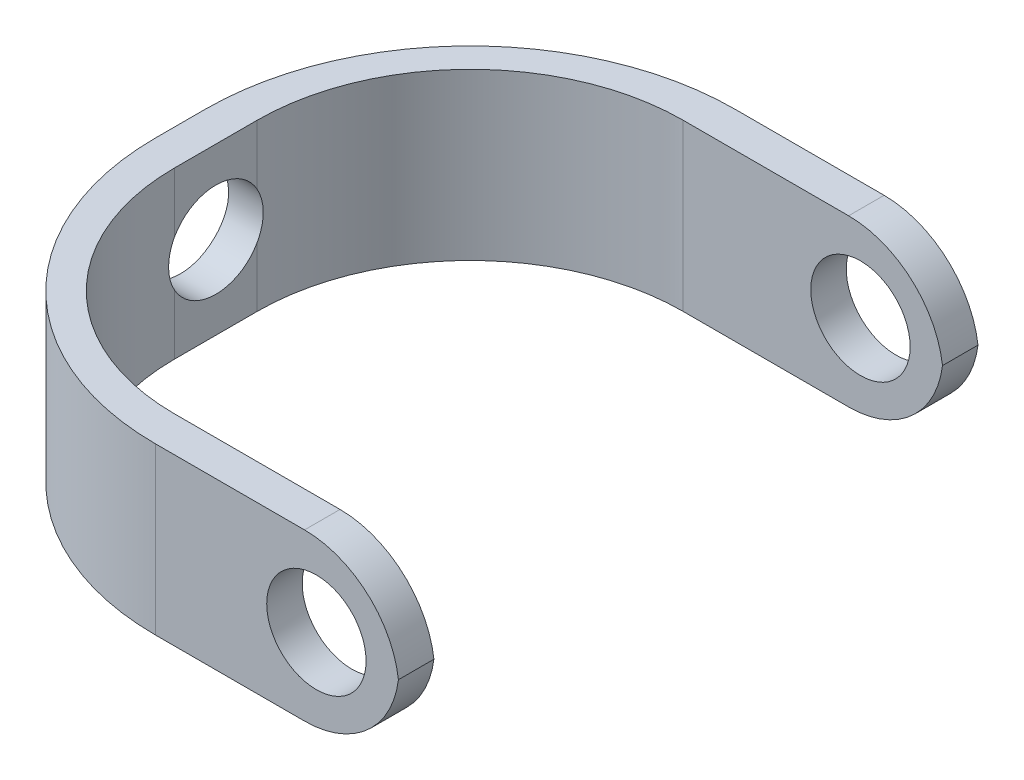
SolidWorks part; units mm, degrees
ref_plane "Спереди" through (0, 0, 0) normal (0, 0, 1) x (1, 0, 0)
ref_plane "Сверху" through (0, 0, 0) normal (0, 1, 0) x (1, 0, 0)
ref_plane "Справа" through (0, 0, 0) normal (1, 0, 0) x (0, 0, -1)
sketch "Эскиз1" plane through (0, 0, 0) normal (0, 1, 0) x (1, 0, 0)
  line L0 (0, 10.75) -> (0, 12.25)
  line L4 (-20, -1.75) -> (-20, 1.75)
  line L5 (0, 10.75) -> (0, 0) construction
  line L6 (0, 0) -> (0, -10.75) construction
  line L7 (0, -12.25) -> (-10.3, -12.25)
  line L9 (0, 12.25) -> (-10.3, 12.25)
  line L11 (0, -10.75) -> (-11, -10.75)
  line L12 (-20, 10.75) -> (-21.5, 10.75) construction
  line L13 (0, -10.75) -> (0, -12.25)
  line L14 (0, 10.75) -> (-11, 10.75)
  line L17 (-21.5, -1.05) -> (-21.5, 1.05)
  arc A0 (-20, -1.75) -> (-11, -10.75) centre (-11, -1.75) ccw
  arc A1 (-20, 1.75) -> (-11, 10.75) centre (-11, 1.75) cw
  arc A2 (-21.5, -1.05) -> (-10.3, -12.25) centre (-10.3, -1.05) ccw
  arc A3 (-21.5, 1.05) -> (-10.3, 12.25) centre (-10.3, 1.05) cw
  point P0 (0, 0)
  point P6 (0, 0)
  dimension "D4" = 9
  dimension "D5" = 11.2
  dimension "D1" = 21.5
  dimension "D2" = 20
  dimension "D3" = 1.5
extrude "Бобышка-Вытянуть1" add sketch "Эскиз1" along normal blind 7
sketch "Эскиз2" plane through (0, 0, 12.25) normal (0, 0, 1) x (1, 0, 0)
  line L0 (-3.5, 3.5) -> (0, 0) construction
  line L1 (-3.5, 3.5) -> (0, 7) construction
  line L2 (-3.5, 5.6) -> (-3.5, 7) construction
  line L3 (-10.3, 7) -> (0, 7) construction
  line L4 (-1.4, 3.5) -> (0, 3.5) construction
  line L5 (0, 7) -> (0, 0) construction
  circle A0 centre (-3.5, 3.5) radius 2.1
  dimension "D1" = 4.2
extrude "Вырез-Вытянуть1" cut sketch "Эскиз2" against normal through all both and the other way through all
fillet "Скругление1" radius 4 4 edges at (0, 0, -11.5) (0, 0, 11.5) (0, 7, -11.5) (0, 7, 11.5)
sketch "Эскиз3" plane through (-21.5, 0, 0) normal (-1, 0, 0) x (0, 0, 1)
  line L0 (0, 0) -> (0, 7) construction
  line L1 (-1.05, 0) -> (1.05, 0) construction
  line L2 (-1.05, 7) -> (1.05, 7) construction
  circle A0 centre (0, 3.5) radius 2
  dimension "D1" = 4
extrude "Вырез-Вытянуть2" cut sketch "Эскиз3" against normal through all both and the other way through all
